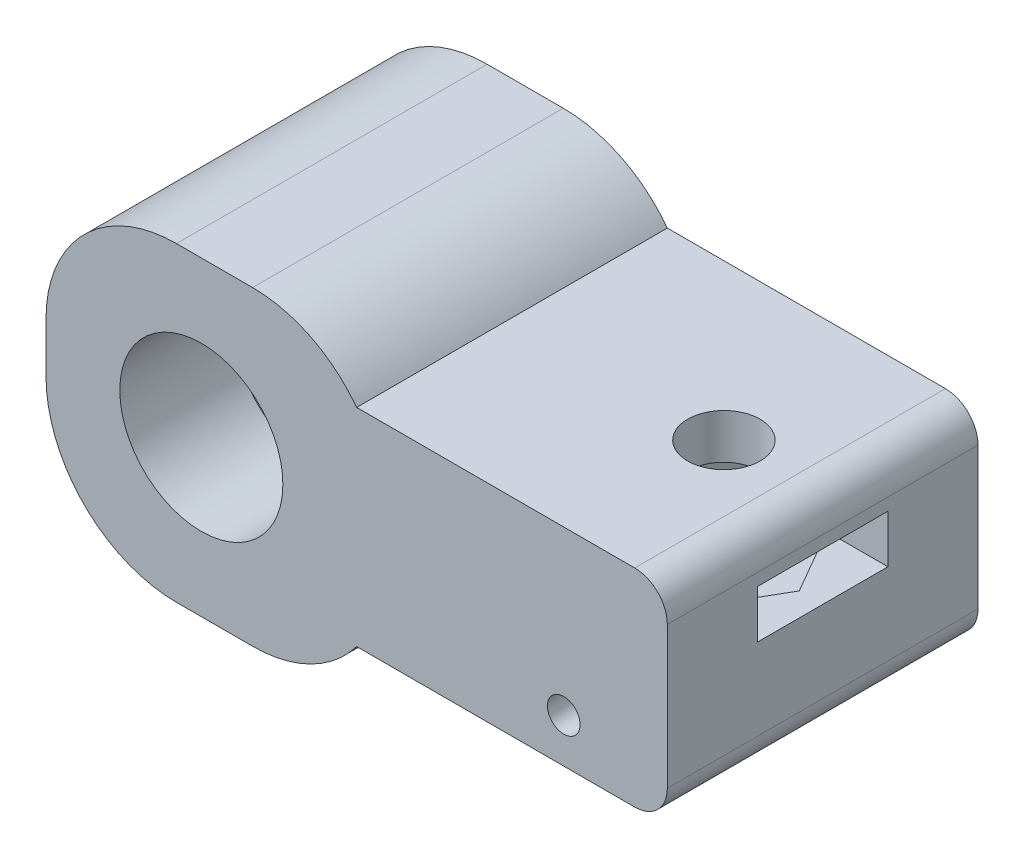
SolidWorks part; units mm, degrees
ref_plane "Front Plane" through (0, 0, 0) normal (0, 0, 1) x (1, 0, 0)
ref_plane "Top Plane" through (0, 0, 0) normal (0, 1, 0) x (1, 0, 0)
ref_plane "Right Plane" through (0, 0, 0) normal (1, 0, 0) x (0, 0, -1)
sketch "Sketch1" plane through (0, 0, 0) normal (0, 0, 1) x (1, 0, 0)
  line L0 (-19.05, 0) -> (19.05, 0) construction
  line L1 (19.05, -9.525) -> (-19.05, -9.525) construction
  line L2 (19.05, -9.525) -> (19.05, 9.525) construction
  line L3 (19.05, 9.525) -> (-19.05, 9.525) construction
  line L4 (-19.05, -9.525) -> (-19.05, 9.525)
  line L5 (19.05, -9.525) -> (-19.05, 9.525) construction
  line L6 (19.05, 9.525) -> (-19.05, -9.525) construction
  line L7 (-19.05, 9.525) -> (0, 9.525)
  line L8 (0, 9.525) -> (0, 6.35)
  line L9 (0, 6.35) -> (19.05, 6.35)
  line L10 (19.05, 6.35) -> (19.05, -6.35)
  line L11 (19.05, -6.35) -> (0, -6.35)
  line L12 (0, -6.35) -> (0, -9.525)
  line L13 (0, -9.525) -> (-19.05, -9.525)
  circle A0 centre (-9.525, 0) radius 3.175
  circle A1 centre (12.7, -3.65) radius 1
  point P0 (0, 0)
  point P18 (19.05, 0)
  dimension "D3" = 6.35
  dimension "D7" = 2
  dimension "D1" = 38.1
  dimension "D2" = 9.525
  dimension "D4" = 6.35
  dimension "D5" = 19.05
  dimension "D6" = 12.7
  dimension "D8" = 19.05
  dimension "D9" = 10
extrude "Boss-Extrude1" add sketch "Sketch1" along normal blind 19.05
sketch "Sketch2" plane through (0, 0, 19.05) normal (0, 0, 1) x (1, 0, 0)
  circle A0 centre (-9.525, 0) radius 5
  dimension "D1" = 10
extrude "Cut-Extrude1" cut sketch "Sketch2" against normal blind 7 contours A0
sketch "Sketch3" plane through (0, 0, 0) normal (0, 0, -1) x (-1, 0, 0)
  circle A0 centre (9.525, 0) radius 6.35
  dimension "D1" = 12.7
extrude "Cut-Extrude2" cut sketch "Sketch3" against normal blind 6.35
sketch "Sketch4" plane through (0, 6.35, 0) normal (0, 1, 0) x (1, 0, 0)
  line L0 (12.9937, -19.05) -> (12.9937, 0) construction
  line L1 (19.05, -19.05) -> (0, -19.05) construction
  line L2 (19.05, 0) -> (0, 0) construction
  line L3 (13.7, 0) -> (11.7, 0) construction
  circle A0 centre (12.9937, -9.525) radius 2.2225
  dimension "D1" = 4.445
extrude "Cut-Extrude3" cut sketch "Sketch4" against normal blind 11
ref_plane "Plane2" through (0, 0.35, 0) normal (0, 1, 0) x (1, 0, 0)
sketch "Sketch6" plane through (0, 0.35, 0) normal (0, 1, 0) x (1, 0, 0)
  line L1 (15.3031, -5.525) -> (10.6843, -5.525)
  line L2 (10.6843, -5.525) -> (8.3749, -9.525)
  line L3 (8.3749, -9.525) -> (10.6843, -13.525)
  line L4 (10.6843, -13.525) -> (15.3031, -13.525)
  line L5 (15.3031, -13.525) -> (17.6125, -9.525)
  line L6 (17.6125, -9.525) -> (15.3031, -5.525)
  line L7 (19.05, 0) -> (0, 0) construction
  circle A0 centre (12.9937, -9.525) radius 4 construction
  dimension "D1" = 8
extrude "Cut-Extrude4" cut sketch "Sketch6" along normal blind 3.25
sketch "Sketch5" plane through (19.05, 0, 0) normal (1, 0, 0) x (0, 0, -1)
  line L0 (-9.525, 6.35) -> (-9.525, -6.35) construction
  line L1 (-19.05, 6.35) -> (0, 6.35) construction
  line L2 (-19.05, -6.35) -> (0, -6.35) construction
  line L3 (-13.525, 3.6) -> (-9.525, 3.6) construction
  line L4 (-13.525, 0.65) -> (-5.525, 0.65)
  line L5 (-13.525, 0.65) -> (-13.525, 3.6)
  line L6 (-13.525, 3.6) -> (-5.525, 3.6)
  line L7 (-5.525, 0.65) -> (-5.525, 3.6)
  line L8 (-13.525, 0.65) -> (-5.525, 3.6) construction
  line L9 (-13.525, 3.6) -> (-5.525, 0.65) construction
  point P6 (-9.525, 2.125)
  dimension "D1" = 8
  dimension "D2" = 2.95
extrude "Cut-Extrude5" cut sketch "Sketch5" against normal up to next
fillet "Fillet1" radius 8 4 edges at (0, 9.525, 9.525) (0, -9.525, 9.525) (-19.05, -9.525, 9.525) (-19.05, 9.525, 9.525)
fillet "Fillet2" radius 2 2 edges at (19.05, -6.35, 9.525) (19.05, 6.35, 9.525)
